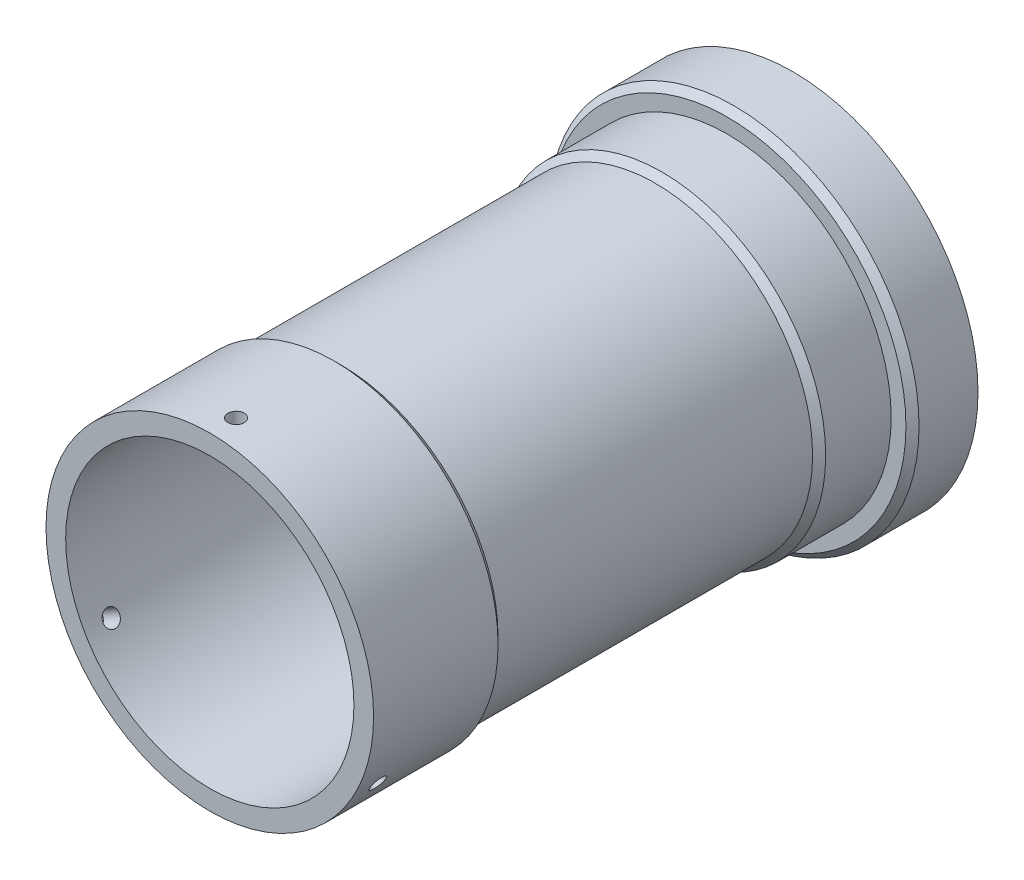
SolidWorks part; units mm, degrees
material "6061 合金"
ref_plane "前视基准面" through (0, 0, 0) normal (0, 0, 1) x (1, 0, 0)
ref_plane "上视基准面" through (0, 0, 0) normal (0, 1, 0) x (1, 0, 0)
ref_plane "右视基准面" through (0, 0, 0) normal (1, 0, 0) x (0, 0, -1)
sketch "草图1" plane through (0, 0, 0) normal (0, 1, 0) x (1, 0, 0)
  line L3 (25, 0) -> (25, 19)
  line L4 (23, 90.5) -> (22, 90.5)
  line L5 (22, 90.5) -> (22, 0)
  line L6 (0, 0) -> (0, 11.7715) construction
  line L12 (25, 19) -> (24, 19)
  line L14 (28.25, 79) -> (28.25, 89)
  line L15 (23, 90.5) -> (23, 89)
  line L16 (23, 89) -> (28.25, 89)
  line L17 (24, 69) -> (24, 19)
  line L18 (28.25, 79) -> (25, 79)
  line L20 (24, 69) -> (25, 69)
  line L21 (25, 79) -> (25, 69)
  line L22 (25, 0) -> (22, 0)
  dimension "D1" = 44
  dimension "D2" = 50
  dimension "D3" = 19
  dimension "D5" = 1.5
  dimension "D6" = 46
  dimension "D8" = 10
  dimension "D9" = 2
  dimension "D11" = 50
  dimension "D12" = 10
  dimension "D14" = 5.25
revolve "旋转1" add sketch "草图1" angle 360 about L6
hole_wizard "M3 螺纹孔1" positions "草图17" profile "草图18" tap size "M3" standard "GB"
sketch "草图17" plane through (0, 0, -89) normal (0, 0, -1) x (-1, 0, 0)
  circle A0 centre (0, 0) radius 25.75 construction
  point P0 (-18.208, 18.208)
  point P12 (18.208, 18.208)
  point P13 (18.208, -18.208)
  point P14 (-18.208, -18.208)
  dimension "D1" = 51.5
  dimension "D2" = 4
sketch "草图18" plane through (18.208, 18.208, -89) normal (1, 0, 0) x (0, 1, 0)
  line L0 (0, 0) -> (0, 7.7511)
  line L1 (0, 7.7511) -> (1.25, 7)
  line L2 (1.25, 7) -> (1.25, 0)
  line L5 (1.25, 0) -> (0, 0)
  line L10 (0, 7.7511) -> (-1.25, 7) construction
  line L11 (0, -6.35) -> (0, 107.95) construction
  dimension "螺纹孔钻头直径" = 2.5
  dimension "螺纹孔钻头深度" = 7
  dimension "导头角度" = 118
cosmetic thread "孔螺蚊线1" parameters "D1"=5, "D2"=3
cosmetic thread "孔螺蚊线2" parameters "D1"=5, "D2"=3
cosmetic thread "孔螺蚊线3" parameters "D1"=5, "D2"=3
cosmetic thread "孔螺蚊线4" parameters "D1"=5, "D2"=3
chamfer "倒角2" distance 1 angle 45 3 edges at (24, 0, -69) (24, 0, -19) (28.25, 0, -79)
hole_wizard "M3 螺纹孔2" positions "草图19" profile "草图20" tap size "M3" standard "GB" end condition through all
sketch "草图19" plane through (0, 0, 0) normal (0, 1, 0) x (1, 0, 0)
  line L0 (0, 0) -> (0, 32.6165) construction
  line L1 (-25, 0) -> (25, 0) construction
  point P7 (0, 4)
  dimension "D1" = 4
sketch "草图20" plane through (0, 0, -4) normal (1, 0, 0) x (0, 0, -1)
  line L0 (0, 0) -> (0, 28.25)
  line L1 (0, 28.25) -> (1.25, 28.25)
  line L2 (1.25, 28.25) -> (1.25, 0)
  line L5 (1.25, 0) -> (0, 0)
  line L11 (0, -6.35) -> (0, 107.95) construction
  dimension "通孔螺纹孔钻头直径" = 2.5
  dimension "通孔螺纹孔钻头深度" = 28.25
cosmetic thread "孔螺蚊线5" parameters "D2"=3
pattern_circular "阵列(圆周)1" count 3 over 360 about axis through (0, 0, 0) along (0, 0, 1) of "M3 螺纹孔2" reverse direction yes
